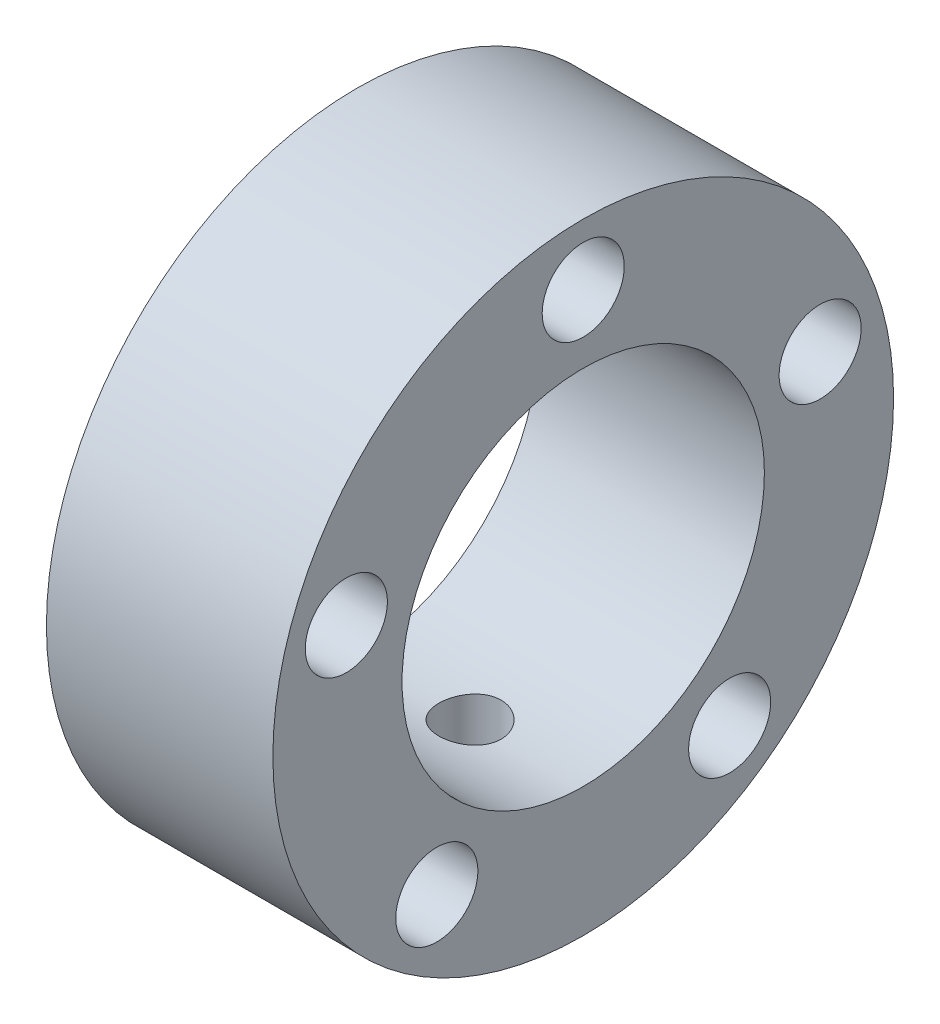
SolidWorks part; units mm, degrees
material "6061 Alloy"
ref_plane "Front Plane" through (0, 0, 0) normal (0, 0, 1) x (1, 0, 0)
ref_plane "Top Plane" through (0, 0, 0) normal (0, 1, 0) x (1, 0, 0)
ref_plane "Right Plane" through (0, 0, 0) normal (1, 0, 0) x (0, 0, -1)
sketch "Sketch1" plane through (0, 0, 0) normal (1, 0, 0) x (0, 0, -1)
  circle A0 centre (0, 0) radius 13.9245
  circle A1 centre (0, 0) radius 8.128
  dimension "D1" = 16.256
  dimension "D2" = 27.8489
extrude "Boss-Extrude1" add sketch "Sketch1" along normal blind 10.16
sketch "Sketch2" plane through (0, 0, 0) normal (-1, 0, 0) x (0, 0, 1)
  line L0 (0, 0) -> (0, 11.176) construction
  circle A0 centre (0, 11.176) radius 1.8415
  circle A1 centre (10.629, 3.4536) radius 1.8415
  circle A2 centre (6.5691, -9.0416) radius 1.8415
  circle A3 centre (-6.5691, -9.0416) radius 1.8415
  circle A4 centre (-10.629, 3.4536) radius 1.8415
  point P14 (0, 0)
  dimension "D1" = 5
  dimension "D2" = 3.683
  dimension "D3" = 11.176
extrude "Cut-Extrude1" cut sketch "Sketch2" against normal through all
sketch "Sketch3" plane through (0, 0, 0) normal (0, 1, 0) x (1, 0, 0)
  line L0 (0, 0) -> (10.16, 0) construction
  line L1 (0, 13.9245) -> (0, -13.9245) construction
  line L2 (10.16, -13.9245) -> (10.16, 13.9245) construction
  circle A0 centre (5.08, 0) radius 1.397
  dimension "D1" = 2.794
extrude "Cut-Extrude2" cut sketch "Sketch3" against normal through all
